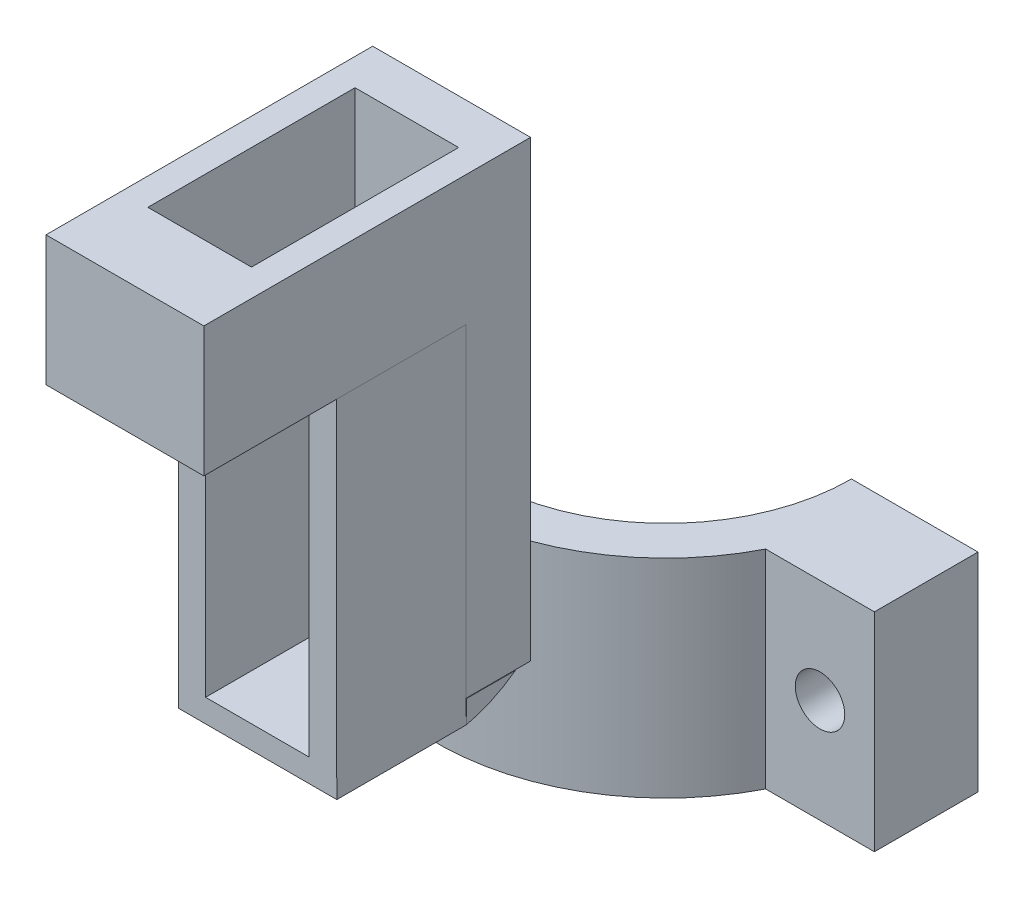
SolidWorks part; units mm, degrees
ref_plane "前基準面" through (0, 0, 0) normal (0, 0, 1) x (1, 0, 0)
ref_plane "上基準面" through (0, 0, 0) normal (0, 1, 0) x (1, 0, 0)
ref_plane "右基準面" through (0, 0, 0) normal (1, 0, 0) x (0, 0, -1)
sketch "草圖1" plane through (0, 0, 0) normal (0, 1, 0) x (1, 0, 0)
  circle A0 centre (0, 0) radius 14.34
  dimension "D1" = 28.68
extrude "伸長-薄件1" add sketch "草圖1" along normal blind 16.05 thin thin type one direction wall 3.29
ref_plane "平面1" through (17.75, 0, 0) normal (1, 0, 0) x (0, 0, -1)
sketch "草圖2" plane through (17.75, 0, 0) normal (1, 0, 0) x (0, 0, -1)
  line L0 (0, -983.95) -> (0, 49016.05) construction
  line L1 (14.34, 16.05) -> (-14.34, 16.05) construction
  line L2 (-1017.63, 8.025) -> (48982.37, 8.025) construction
  line L3 (-17.63, 16.05) -> (-17.63, 0) construction
  line L5 (-8, 16.05) -> (8, 16.05)
  line L6 (-8, 16.05) -> (-8, 0)
  line L7 (-8, 0) -> (8, 0)
  line L8 (8, 16.05) -> (8, 0)
  line L9 (-8, 16.05) -> (8, 0) construction
  line L10 (-8, 0) -> (8, 16.05) construction
  point P5 (0, 16.05)
  point P6 (0, 8.025)
  point P10 (-17.63, 8.025)
  dimension "D1" = 0
  dimension "D2" = 16
extrude "填料-伸長1" add sketch "草圖2" along normal blind 9.77 and the other way blind 3
sketch "草圖3" plane through (0, 16.05, 0) normal (0, 1, 0) x (1, 0, 0)
  line L0 (14.34, 0) -> (27.52, 0) construction
  line L1 (27.52, 8) -> (27.52, -8) construction
  line L2 (15.7104, -8) -> (27.52, -8) construction
  line L3 (27.52, 8) -> (24.11, 8)
  line L4 (27.52, 8) -> (27.52, -8)
  line L5 (27.52, -8) -> (24.11, -8)
  line L6 (24.11, 8) -> (24.11, -8)
  circle A0 centre (0, 0) radius 14.34 construction
  dimension "D1" = 3.41
extrude "除料-伸長1" cut sketch "草圖3" against normal through all
sketch "草圖4" plane through (0, 0, 8) normal (0, 0, 1) x (1, 0, 0)
  line L0 (19.9102, -983.95) -> (19.9102, 49016.05) construction
  line L1 (15.7104, 16.05) -> (24.11, 16.05) construction
  line L2 (-984.2896, 8.025) -> (49015.7104, 8.025) construction
  line L3 (15.7104, 0) -> (15.7104, 16.05) construction
  circle A0 centre (19.9102, 8.025) radius 1.91
  point P5 (19.9102, 16.05)
  point P10 (15.7104, 8.025)
  dimension "D1" = 3.82
extrude "除料-伸長2" cut sketch "草圖4" against normal through all
ref_plane "平面2" through (0, 0, 17.75) normal (0, 0, 1) x (1, 0, 0)
sketch "草圖5" plane through (0, 0, 17.75) normal (0, 0, 1) x (1, 0, 0)
  line L0 (-1017.63, 8.025) -> (48982.37, 8.025) construction
  line L1 (-17.63, 16.05) -> (-17.63, 0) construction
  line L2 (0, -983.95) -> (0, 49016.05) construction
  line L3 (14.34, 16.05) -> (-14.34, 16.05) construction
  line L5 (-6.095, 16.2886) -> (6.095, 16.2886)
  line L6 (-6.095, 16.2886) -> (-6.095, 8.025)
  line L7 (-6.095, 8.025) -> (6.095, 8.025)
  line L8 (6.095, 16.2886) -> (6.095, 8.025)
  line L9 (-6.095, 16.2886) -> (6.095, 8.025) construction
  line L10 (-6.095, 8.025) -> (6.095, 16.2886) construction
  point P5 (-17.63, 8.025)
  point P6 (0, 12.1568)
  point P10 (0, 16.05)
  dimension "D1" = 12.19
extrude "填料-伸長2" add sketch "草圖5" along normal blind 4 and the other way blind 2.77
sketch "草圖6" plane through (0, 16.2886, 0) normal (0, 1, 0) x (1, 0, 0)
  line L1 (-6.095, -14.98) -> (6.095, -14.98)
  line L2 (-6.095, -14.98) -> (-6.095, -21.75)
  line L3 (-6.095, -21.75) -> (6.095, -21.75)
  line L4 (6.095, -14.98) -> (6.095, -21.75)
extrude "填料-伸長3" add sketch "草圖6" along normal blind 63
sketch "草圖8" plane through (0, 79.2886, 0) normal (0, 1, 0) x (1, 0, 0)
  line L1 (-6.095, -21.75) -> (6.095, -21.75)
  line L2 (-6.095, -21.75) -> (-6.095, -14.98)
  line L3 (-6.095, -14.98) -> (6.095, -14.98)
  line L4 (6.095, -21.75) -> (6.095, -14.98)
extrude "填料-伸長4" add sketch "草圖8" along normal blind 0.16
ref_plane "平面3" through (-17.75, 0, 0) normal (1, 0, 0) x (0, 0, -1)
sketch "草圖12" plane through (-17.75, 0, 0) normal (1, 0, 0) x (0, 0, -1)
  line L0 (0.5435, -983.95) -> (0.5435, 49016.05) construction
  line L1 (17.63, 16.05) -> (-16.5429, 16.05) construction
  line L2 (-982.37, 8.025) -> (49017.63, 8.025) construction
  line L3 (17.63, 0) -> (17.63, 16.05) construction
  line L5 (8.5435, 16.05) -> (-7.4565, 16.05)
  line L6 (8.5435, 16.05) -> (8.5435, 0)
  line L7 (8.5435, 0) -> (-7.4565, 0)
  line L8 (-7.4565, 16.05) -> (-7.4565, 0)
  line L9 (8.5435, 16.05) -> (-7.4565, 0) construction
  line L10 (8.5435, 0) -> (-7.4565, 16.05) construction
  point P5 (0.5435, 16.05)
  point P6 (0.5435, 8.025)
  point P10 (17.63, 8.025)
  dimension "D1" = 0
  dimension "D2" = 16
extrude "填料-伸長5" add sketch "草圖12" along normal blind 3.16 and the other way blind 10
sketch "草圖13" plane through (0, 16.05, 0) normal (0, 1, 0) x (1, 0, 0)
  line L0 (-14.34, 0) -> (-27.75, 0) construction
  line L1 (-27.75, 8.5435) -> (-27.75, -7.4565) construction
  line L2 (-27.75, -7.4565) -> (-15.9755, -7.4565) construction
  line L3 (-27.75, 8.5435) -> (-26.54, 8.5435)
  line L4 (-27.75, 8.5435) -> (-27.75, -7.4565)
  line L5 (-27.75, -7.4565) -> (-26.54, -7.4565)
  line L6 (-26.54, 8.5435) -> (-26.54, -7.4565)
  circle A0 centre (0, 0) radius 14.34 construction
  dimension "D1" = 1.21
extrude "除料-伸長3" cut sketch "草圖13" against normal through all
sketch "草圖14" plane through (0, 0, -8.5435) normal (0, 0, -1) x (-1, 0, 0)
  line L0 (20.9808, -983.95) -> (20.9808, 49016.05) construction
  line L1 (26.54, 16.05) -> (15.4216, 16.05) construction
  line L2 (-973.46, 8.025) -> (49026.54, 8.025) construction
  line L3 (26.54, 0) -> (26.54, 16.05) construction
  circle A0 centre (20.9808, 8.025) radius 1.91
  point P5 (20.9808, 16.05)
  point P10 (26.54, 8.025)
  dimension "D1" = 3.82
extrude "除料-伸長4" cut sketch "草圖14" against normal through all
sketch "草圖15" plane through (0, 79.4486, 0) normal (0, 1, 0) x (1, 0, 0)
  line L0 (6.095, -14.98) -> (-6.095, -14.98) construction
  circle A0 centre (0, -14.98) radius 4.05
  dimension "D1" = 8.1
extrude "除料-伸長5" cut sketch "草圖15" against normal blind 24
sketch "草圖16" plane through (0, 16.05, 0) normal (0, 1, 0) x (1, 0, 0)
  line L0 (24.11, 8) -> (24.11, -8) construction
  line L1 (24.11, 0) -> (-32.2905, 0)
  line L2 (24.11, 0) -> (24.11, 19.935)
  line L3 (24.11, 19.935) -> (-32.2905, 19.935)
  line L4 (-32.2905, 0) -> (-32.2905, 19.935)
extrude "除料-伸長6" cut sketch "草圖16" against normal through all
sketch "草圖17" plane through (0, 0, 21.75) normal (0, 0, 1) x (1, 0, 0)
  line L1 (-6.095, 8.025) -> (6.095, 8.025)
  line L2 (-6.095, 8.025) -> (-6.095, 79.4486)
  line L3 (-6.095, 79.4486) -> (6.095, 79.4486)
  line L4 (6.095, 8.025) -> (6.095, 79.4486)
extrude "填料-伸長7" add sketch "草圖17" along normal blind 25
sketch "草圖18" plane through (-6.095, 0, 0) normal (-1, 0, 0) x (0, 0, 1)
  line L0 (14.98, 79.4486) -> (46.75, 79.4486) construction
  line L1 (14.98, 16.05) -> (41.7734, 16.05)
  line L2 (14.98, 16.05) -> (14.98, 79.4486)
  line L3 (14.98, 79.4486) -> (41.7734, 79.4486)
  line L4 (41.7734, 16.05) -> (41.7734, 79.4486)
extrude "除料-伸長7" cut sketch "草圖18" against normal blind 25
sketch "草圖19" plane through (0, 79.4486, 0) normal (0, 1, 0) x (1, 0, 0)
  line L0 (6.095, -41.7734) -> (-6.095, -41.7734) construction
  circle A0 centre (0, -41.7734) radius 4
  dimension "D1" = 8
extrude "除料-伸長8" cut sketch "草圖19" against normal blind 24
sketch "草圖20" plane through (6.095, 0, 0) normal (1, 0, 0) x (0, 0, -1)
  line L0 (-41.7734, 16.05) -> (-41.7734, 8.025)
  line L1 (-16.5429, 8.025) -> (-46.75, 8.025) construction
  line L2 (-41.7734, 8.025) -> (-46.75, 8.025)
  line L3 (-46.75, 8.025) -> (-46.75, 79.4486)
  line L4 (-46.75, 79.4486) -> (-41.7734, 79.4486)
  line L5 (-41.7734, 79.4486) -> (-41.7734, 16.05)
extrude "除料-伸長9" cut sketch "草圖20" against normal blind 29
sketch "草圖23" plane through (0, 8.025, 0) normal (0, -1, 0) x (1, 0, 0)
  line L0 (-6.095, 41.7734) -> (-6.095, 17.75)
  line L1 (23.6775, 17.75) -> (-23.6775, 17.75) construction
  line L2 (-6.095, 16.5429) -> (-6.095, 41.7734) construction
  line L3 (-6.095, 17.75) -> (6.1383, 17.75)
  line L4 (6.1383, 17.75) -> (6.095, 41.7734)
  line L5 (6.095, 41.7734) -> (-6.095, 41.7734)
extrude "填料-伸長9" add sketch "草圖23" along normal blind 2
fillet "圓角1" radius 10 1 edges at (0.0216, 6.025, 17.75)
sketch "草圖24" plane through (0, 16.05, 0) normal (0, 1, 0) x (1, 0, 0)
  line L0 (6.095, -41.7734) -> (6.095, -16.5429) construction
  line L1 (-6.095, -16.5429) -> (6.095, -16.5429)
  line L2 (-6.095, -16.5429) -> (-6.095, -21.5429)
  line L3 (-6.095, -21.5429) -> (6.095, -21.5429)
  line L4 (6.095, -16.5429) -> (6.095, -21.5429)
  dimension "D1" = 5
extrude "填料-伸長10" add sketch "草圖24" along normal blind 27
sketch "草圖25" plane through (-6.095, 0, 0) normal (-1, 0, 0) x (0, 0, 1)
  line L0 (21.5429, 16.05) -> (41.7734, 16.05)
  line L1 (41.7734, 16.05) -> (41.7734, 6.025)
  line L2 (41.7734, 6.025) -> (21.5429, 6.025)
  line L3 (21.5429, 6.025) -> (21.5429, 16.05)
sketch "草圖27" plane through (0, 0, 21.5429) normal (0, 0, 1) x (1, 0, 0)
  line L0 (6.095, 43.05) -> (6.095, 16.05) construction
  line L1 (-6.095, 43.05) -> (6.095, 43.05)
  line L2 (-6.095, 43.05) -> (-6.095, 33.02)
  line L3 (-6.095, 33.02) -> (6.095, 33.02)
  line L4 (6.095, 43.05) -> (6.095, 33.02)
  dimension "D1" = 10.03
extrude "填料-伸長11" add sketch "草圖27" along normal blind 20.23
sketch "草圖21" plane through (0, 16.05, 0) normal (0, 1, 0) x (1, 0, 0)
  line L0 (0, -1014.34) -> (0, 48985.66) construction
  line L2 (-4, -20) -> (4, -20)
  line L3 (-4, -20) -> (-4, -36)
  line L4 (-4, -36) -> (4, -36)
  line L5 (4, -20) -> (4, -36)
  line L6 (-4, -20) -> (4, -36) construction
  line L7 (-4, -36) -> (4, -20) construction
  arc A0 (-14.34, 0) -> (14.34, 0) centre (0, 0) ccw construction
  point P1 (0, -28)
  point P6 (0, -14.34)
  dimension "D1" = 20
  dimension "D2" = 16
  dimension "D3" = 8
extrude "除料-伸長10" cut sketch "草圖21" against normal blind 8 and the other way blind 45.23
extrude "除料-伸長12" cut sketch "草圖25" against normal blind 20.23
sketch "草圖31" plane through (0, 0, 36) normal (0, 0, -1) x (-1, 0, 0)
  line L0 (4, 43.05) -> (4, 33.02) construction
  line L1 (-4, 33.02) -> (4, 33.02)
  line L2 (-4, 33.02) -> (-4, 35.05)
  line L3 (-4, 35.05) -> (4, 35.05)
  line L4 (4, 33.02) -> (4, 35.05)
  dimension "D1" = 2.03
extrude "填料-伸長13" add sketch "草圖31" along normal blind 16.23
sketch "草圖33" plane through (0, 0, 21.5429) normal (0, 0, 1) x (1, 0, 0)
  line L0 (-6.095, 33.02) -> (-4, 33.02)
  line L1 (-4, 33.02) -> (-4, 8.05)
  line L2 (-4, 8.05) -> (4, 8.05)
  line L3 (4, 8.05) -> (4, 33.02)
  line L4 (4, 33.02) -> (6.095, 33.02)
  line L5 (6.095, 33.02) -> (6.1315, 6.2716)
  line L6 (6.1315, 6.2716) -> (-6.095, 6.2716)
  line L7 (-6.095, 6.2716) -> (6.1315, 6.2716) construction
  line L8 (-6.095, 33.02) -> (-6.095, 6.2716) construction
  line L9 (-6.095, 6.2716) -> (-6.095, 33.02)
extrude "填料-伸長17" add sketch "草圖33" along normal blind 10
